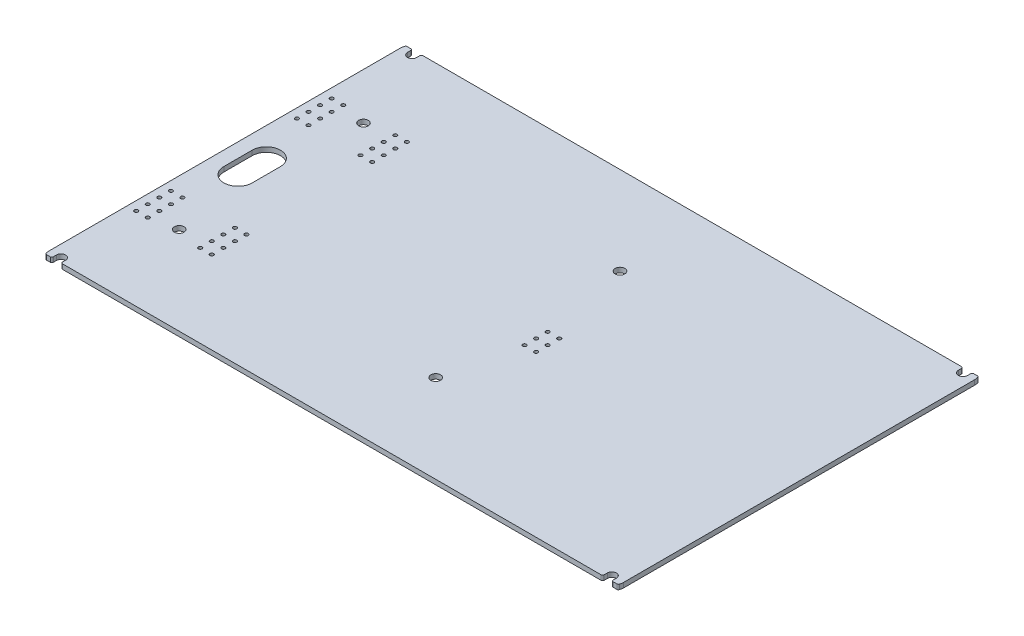
SolidWorks part; units mm, degrees
material "A-Glass Fiber"
ref_plane "Front Plane" through (0, 0, 0) normal (0, 0, 1) x (1, 0, 0)
ref_plane "Top Plane" through (0, 0, 0) normal (0, 1, 0) x (1, 0, 0)
ref_plane "Right Plane" through (0, 0, 0) normal (1, 0, 0) x (0, 0, -1)
sketch "Sketch1" plane through (0, 0, 0) normal (0, 1, 0) x (1, 0, 0)
  line L0 (0, 0) -> (133.1949, 0) construction
  line L2 (-55.9843, -57.8231) -> (-55.9843, 57.8231)
  line L4 (133.1949, -57.8231) -> (133.1949, 57.8231)
  line L8 (-55.6615, 59.3713) -> (132.872, 59.3713)
  line L9 (-55.6615, -59.3713) -> (132.872, -59.3713)
  arc A0 (-55.9843, 57.8231) -> (-55.6615, 59.3713) centre (-52.1108, 57.8231) cw
  arc A1 (132.872, 59.3713) -> (133.1949, 57.8231) centre (129.3214, 57.8231) cw
  arc A2 (133.1949, -57.8231) -> (132.872, -59.3713) centre (129.3214, -57.8231) cw
  arc A3 (-55.6615, -59.3713) -> (-55.9843, -57.8231) centre (-52.1108, -57.8231) cw
  arc A8 (31.0353, 66.8607) -> (46.1753, 66.8607) centre (38.6053, 66.9417) ccw construction
  circle A9 centre (-52.1108, -57.8231) radius 3.8735 construction
  circle A10 centre (129.3214, 57.8231) radius 3.8735 construction
  circle A11 centre (-52.1108, 57.8231) radius 3.8735 construction
  circle A12 centre (129.3214, -57.8231) radius 3.8735 construction
  arc A13 (46.1753, -66.8607) -> (31.0353, -66.8607) centre (38.6053, -66.9417) ccw construction
  point P1 (0, 0)
  point P16 (133.1949, 57.8231)
  point P17 (133.1949, 57.8231)
extrude "Boss-Extrude1" add sketch "Sketch1" against normal blind 1.5875
sketch "Sketch2" plane through (0, 0, 0) normal (0, 1, 0) x (1, 0, 0)
  circle A35 centre (-40.6725, -30.35) radius 1.5875
  circle A36 centre (-40.6725, -30.35) radius 1.5875
  circle A37 centre (-40.6725, 30.35) radius 1.5875
  circle A38 centre (-40.6725, 30.35) radius 1.5875
  circle A39 centre (43.8275, 30.35) radius 1.5875
  circle A40 centre (43.8275, 30.35) radius 1.5875
  circle A41 centre (43.8275, -30.35) radius 1.5875
  circle A42 centre (43.8275, -30.35) radius 1.5875
  dimension "D27" = 0
  dimension "D28" = 0
  dimension "D29" = 0
  dimension "D30" = 0
extrude "Cut-Extrude1" cut sketch "Sketch2" against normal through all
sketch "Sketch3" plane through (0, 0, 0) normal (0, 1, 0) x (1, 0, 0)
  line L5 (-46.6035, 4.285) -> (-46.6035, -5.035) construction
  line L6 (-41.9335, 4.285) -> (-41.9335, -5.035)
  line L7 (-51.2735, 4.285) -> (-51.2735, -5.035)
  line L17 (-43.2035, 3.375) -> (-41.9335, 3.375) construction
  line L18 (-44.8535, 7.2) -> (-44.1998, 8.2889) construction
  line L19 (-46.6035, 7.2) -> (-46.6035, 8.955) construction
  line L20 (-44.8535, 7.2) -> (-48.3535, 7.2) construction
  line L21 (-46.6035, -7.95) -> (-46.6035, -9.705) construction
  line L22 (-48.3535, -7.95) -> (-44.8535, -7.95) construction
  arc A13 (-41.9335, 4.285) -> (-51.2735, 4.285) centre (-46.6035, 4.285) ccw
  arc A14 (-51.2735, -5.035) -> (-41.9335, -5.035) centre (-46.6035, -5.035) ccw
  arc A17 (-44.8535, 0.46) -> (-44.8535, 6.29) centre (-46.6035, 3.375) ccw construction
  point P2 (-46.6035, -0.375)
  dimension "D1" = 1.27
extrude "Cut-Extrude2" cut sketch "Sketch3" against normal through all
sketch "Sketch4" plane through (0, -1.5875, 0) normal (0, -1, 0) x (1, 0, 0)
  line L4 (-34.35, -10.348) -> (-39.27, -10.348)
  line L5 (-34.35, -25.08) -> (-34.35, -10.348)
  line L6 (-39.27, -25.08) -> (-34.35, -25.08)
  line L7 (-39.27, -10.348) -> (-39.27, -25.08)
  line L8 (-34.35, -10.348) -> (-39.27, -10.348)
  line L9 (-34.35, -25.08) -> (-34.35, -10.348)
  line L10 (-39.27, -25.08) -> (-34.35, -25.08)
  line L11 (-39.27, -10.348) -> (-39.27, -25.08)
  line L12 (-34.35, 25.63) -> (-39.27, 25.63)
  line L13 (-34.35, 10.898) -> (-34.35, 25.63)
  line L14 (-39.27, 10.898) -> (-34.35, 10.898)
  line L15 (-39.27, 25.63) -> (-39.27, 10.898)
  line L16 (-34.35, 25.63) -> (-39.27, 25.63)
  line L17 (-34.35, 10.898) -> (-34.35, 25.63)
  line L18 (-39.27, 10.898) -> (-34.35, 10.898)
  line L19 (-39.27, 25.63) -> (-39.27, 10.898)
  line L20 (-44.42, 10.898) -> (-39.5, 10.898)
  line L21 (-39.5, 10.898) -> (-39.5, 25.63)
  line L22 (-39.5, 25.63) -> (-44.42, 25.63)
  line L23 (-44.42, 25.63) -> (-44.42, 10.898)
  line L24 (-44.42, 10.898) -> (-39.5, 10.898)
  line L25 (-39.5, 10.898) -> (-39.5, 25.63)
  line L26 (-39.5, 25.63) -> (-44.42, 25.63)
  line L27 (-44.42, 25.63) -> (-44.42, 10.898)
  line L28 (-39.5, -10.348) -> (-44.42, -10.348)
  line L29 (-39.5, -25.08) -> (-39.5, -10.348)
  line L30 (-44.42, -25.08) -> (-39.5, -25.08)
  line L31 (-44.42, -10.348) -> (-44.42, -25.08)
  line L32 (-39.5, -10.348) -> (-44.42, -10.348)
  line L33 (-39.5, -25.08) -> (-39.5, -10.348)
  line L34 (-44.42, -25.08) -> (-39.5, -25.08)
  line L35 (-44.42, -10.348) -> (-44.42, -25.08)
  line L36 (35.46, 13.148) -> (40.38, 13.148)
  line L37 (35.46, 27.88) -> (35.46, 13.148)
  line L38 (40.38, 27.88) -> (35.46, 27.88)
  line L39 (40.38, 13.148) -> (40.38, 27.88)
  line L40 (35.46, 13.148) -> (40.38, 13.148)
  line L41 (35.46, 27.88) -> (35.46, 13.148)
  line L42 (40.38, 27.88) -> (35.46, 27.88)
  line L43 (40.38, 13.148) -> (40.38, 27.88)
  dimension "D1" = 0
  dimension "D2" = 0
  dimension "D3" = 0
  dimension "D4" = 0
  dimension "D5" = 0
sketch "Sketch6" plane through (0, -1.5875, 0) normal (0, -1, 0) x (1, 0, 0)
  line L0 (-20.19, 27.65) -> (-20.19, 33.65) construction
  line L1 (-20.19, 33.65) -> (-14.19, 33.65) construction
  line L2 (-14.19, 33.65) -> (-14.19, 27.65) construction
  line L3 (-14.19, 27.65) -> (-20.19, 27.65) construction
  line L4 (33.69, -6.45) -> (33.69, -22.45)
  line L5 (54.59, -6.45) -> (33.69, -6.45)
  line L6 (54.59, -22.45) -> (54.59, -6.45)
  line L7 (33.69, -22.45) -> (54.59, -22.45)
  line L8 (33.69, -6.45) -> (33.69, -22.45)
  line L9 (54.59, -6.45) -> (33.69, -6.45)
  line L10 (54.59, -22.45) -> (54.59, -6.45)
  line L11 (33.69, -22.45) -> (54.59, -22.45)
  line L20 (-8.69, 27.65) -> (-8.69, 33.65) construction
  line L21 (-8.69, 33.65) -> (-2.69, 33.65) construction
  line L22 (-2.69, 33.65) -> (-2.69, 27.65) construction
  line L23 (-2.69, 27.65) -> (-8.69, 27.65) construction
  line L24 (-20.19, 27.65) -> (-20.19, 33.65)
  line L25 (-20.19, 33.65) -> (-14.19, 33.65)
  line L26 (-14.19, 33.65) -> (-14.19, 27.65)
  line L27 (-14.19, 27.65) -> (-20.19, 27.65)
  line L28 (-8.69, 27.65) -> (-8.69, 33.65)
  line L29 (-8.69, 33.65) -> (-2.69, 33.65)
  line L30 (-2.69, 33.65) -> (-2.69, 27.65)
  line L31 (-2.69, 27.65) -> (-8.69, 27.65)
  line L80 (55.31, -35.15) -> (55.31, 35.15)
  line L82 (55.31, 35.15) -> (-55.31, 35.15)
  line L84 (-55.31, 35.15) -> (-55.31, -35.15)
  line L86 (-55.31, -35.15) -> (55.31, -35.15)
  line L92 (55.31, -35.15) -> (55.31, 35.15)
  line L94 (55.31, 35.15) -> (-55.31, 35.15)
  line L96 (-55.31, 35.15) -> (-55.31, -35.15)
  line L98 (-55.31, -35.15) -> (55.31, -35.15)
  circle A0 centre (-17.19, 30.65) radius 1.75 construction
  circle A1 centre (-5.69, 30.65) radius 1.75 construction
  circle A2 centre (-17.19, 30.65) radius 1.75
  circle A3 centre (-5.69, 30.65) radius 1.75
  dimension "D1" = 0
  dimension "D2" = 0
sketch "Sketch7" plane through (0, -1.5875, 0) normal (0, -1, 0) x (1, 0, 0)
  circle A1 centre (49.2175, 6.483) radius 0.6
  circle A2 centre (49.2175, 6.483) radius 0.6
  circle A3 centre (-49.1085, -32.125) radius 0.6
  circle A4 centre (-49.1085, -32.125) radius 0.6
  circle A5 centre (-28.1535, -32.125) radius 0.6
  circle A6 centre (-28.1535, -32.125) radius 0.6
  circle A7 centre (-28.1535, 20.707) radius 0.6
  circle A8 centre (-28.1535, 20.707) radius 0.6
  circle A9 centre (-49.2355, 20.707) radius 0.6
  circle A10 centre (-49.2355, 20.707) radius 0.6
  circle A11 centre (-31.9635, 20.707) radius 0.6
  circle A12 centre (-31.9635, 20.707) radius 0.6
  circle A13 centre (-53.0455, 20.707) radius 0.6
  circle A14 centre (-53.0455, 20.707) radius 0.6
  circle A15 centre (-31.9635, 28.327) radius 0.6
  circle A16 centre (-31.9635, 28.327) radius 0.6
  circle A17 centre (-53.0455, 28.327) radius 0.6
  circle A18 centre (-53.0455, 28.327) radius 0.6
  circle A19 centre (-31.9635, 24.517) radius 0.6
  circle A20 centre (-31.9635, 24.517) radius 0.6
  circle A21 centre (-53.0455, 24.517) radius 0.6
  circle A22 centre (-53.0455, 24.517) radius 0.6
  circle A23 centre (-31.9635, -28.315) radius 0.6
  circle A24 centre (-31.9635, -28.315) radius 0.6
  circle A25 centre (-52.9185, -28.315) radius 0.6
  circle A26 centre (-52.9185, -28.315) radius 0.6
  circle A27 centre (-31.9635, -32.125) radius 0.6
  circle A28 centre (-31.9635, -32.125) radius 0.6
  circle A29 centre (-52.9185, -32.125) radius 0.6
  circle A30 centre (-52.9185, -32.125) radius 0.6
  circle A31 centre (-28.1535, 24.517) radius 0.6
  circle A32 centre (-28.1535, 24.517) radius 0.6
  circle A33 centre (-49.2355, 24.517) radius 0.6
  circle A34 centre (-49.2355, 24.517) radius 0.6
  circle A35 centre (-31.9635, 32.137) radius 0.6
  circle A36 centre (-31.9635, 32.137) radius 0.6
  circle A37 centre (-53.0455, 32.137) radius 0.6
  circle A38 centre (-53.0455, 32.137) radius 0.6
  circle A39 centre (-31.9635, -20.695) radius 0.6
  circle A40 centre (-31.9635, -20.695) radius 0.6
  circle A41 centre (-52.9185, -20.695) radius 0.6
  circle A42 centre (-52.9185, -20.695) radius 0.6
  circle A43 centre (-31.9635, -24.505) radius 0.6
  circle A44 centre (-31.9635, -24.505) radius 0.6
  circle A45 centre (-52.9185, -24.505) radius 0.6
  circle A46 centre (-52.9185, -24.505) radius 0.6
  circle A47 centre (-28.1535, 32.137) radius 0.6
  circle A48 centre (-28.1535, 32.137) radius 0.6
  circle A49 centre (-49.2355, 32.137) radius 0.6
  circle A50 centre (-49.2355, 32.137) radius 0.6
  circle A51 centre (-28.1535, 28.327) radius 0.6
  circle A52 centre (-28.1535, 28.327) radius 0.6
  circle A53 centre (-49.2355, 28.327) radius 0.6
  circle A54 centre (-49.2355, 28.327) radius 0.6
  circle A55 centre (-28.1535, -24.505) radius 0.6
  circle A56 centre (-28.1535, -24.505) radius 0.6
  circle A57 centre (-49.1085, -24.505) radius 0.6
  circle A58 centre (-49.1085, -24.505) radius 0.6
  circle A59 centre (-28.1535, -28.315) radius 0.6
  circle A60 centre (-28.1535, -28.315) radius 0.6
  circle A61 centre (-49.1085, -28.315) radius 0.6
  circle A62 centre (-49.1085, -28.315) radius 0.6
  circle A63 centre (49.2175, 2.673) radius 0.6
  circle A64 centre (49.2175, 2.673) radius 0.6
  circle A65 centre (53.0275, -1.137) radius 0.6
  circle A66 centre (53.0275, -1.137) radius 0.6
  circle A67 centre (53.0275, 2.673) radius 0.6
  circle A68 centre (53.0275, 2.673) radius 0.6
  circle A69 centre (53.0275, 6.483) radius 0.6
  circle A70 centre (53.0275, 6.483) radius 0.6
  circle A71 centre (-28.1535, -20.695) radius 0.6
  circle A72 centre (-28.1535, -20.695) radius 0.6
  circle A73 centre (-49.1085, -20.695) radius 0.6
  circle A74 centre (-49.1085, -20.695) radius 0.6
  circle A75 centre (49.2175, -1.137) radius 0.6
  circle A76 centre (49.2175, -1.137) radius 0.6
  dimension "D1" = 0
  dimension "D2" = 0
  dimension "D3" = 0
  dimension "D4" = 0
  dimension "D5" = 0
  dimension "D6" = 0
  dimension "D7" = 0
  dimension "D8" = 0
  dimension "D9" = 0
  dimension "D10" = 0
  dimension "D11" = 0
  dimension "D12" = 0
  dimension "D13" = 0
  dimension "D14" = 0
  dimension "D15" = 0
  dimension "D16" = 0
  dimension "D17" = 0
  dimension "D18" = 0
  dimension "D19" = 0
  dimension "D20" = 0
  dimension "D21" = 0
  dimension "D22" = 0
  dimension "D23" = 0
  dimension "D24" = 0
  dimension "D25" = 0
  dimension "D26" = 0
  dimension "D27" = 0
  dimension "D28" = 0
  dimension "D29" = 0
  dimension "D30" = 0
  dimension "D31" = 0
  dimension "D32" = 0
  dimension "D33" = 0
  dimension "D34" = 0
  dimension "D35" = 0
  dimension "D36" = 0
  dimension "D37" = 0
  dimension "D38" = 0
extrude "Cut-Extrude3" cut sketch "Sketch7" against normal through all
sketch "Sketch8" plane through (0, -1.5875, 0) normal (0, -1, 0) x (1, 0, 0)
  line L4 (-47.9085, -18.395) -> (-54.7585, -18.395)
  line L5 (-47.9085, -34.425) -> (-47.9085, -18.395)
  line L6 (-54.7585, -34.425) -> (-47.9085, -34.425)
  line L7 (-54.7585, -18.395) -> (-54.7585, -34.425)
  line L8 (-47.9085, -18.395) -> (-54.7585, -18.395)
  line L9 (-47.9085, -34.425) -> (-47.9085, -18.395)
  line L10 (-54.7585, -34.425) -> (-47.9085, -34.425)
  line L11 (-54.7585, -18.395) -> (-54.7585, -34.425)
  line L12 (-54.8855, 18.407) -> (-48.0355, 18.407)
  line L13 (-48.0355, 18.407) -> (-48.0355, 34.437)
  line L14 (-48.0355, 34.437) -> (-54.8855, 34.437)
  line L15 (-54.8855, 34.437) -> (-54.8855, 18.407)
  line L16 (-54.8855, 18.407) -> (-48.0355, 18.407)
  line L17 (-48.0355, 18.407) -> (-48.0355, 34.437)
  line L18 (-48.0355, 34.437) -> (-54.8855, 34.437)
  line L19 (-54.8855, 34.437) -> (-54.8855, 18.407)
  line L20 (-33.8035, -18.395) -> (-33.8035, -34.425)
  line L21 (-33.8035, -34.425) -> (-26.9535, -34.425)
  line L22 (-26.9535, -34.425) -> (-26.9535, -18.395)
  line L23 (-26.9535, -18.395) -> (-33.8035, -18.395)
  line L24 (-33.8035, -18.395) -> (-33.8035, -34.425)
  line L25 (-33.8035, -34.425) -> (-26.9535, -34.425)
  line L26 (-26.9535, -34.425) -> (-26.9535, -18.395)
  line L27 (-26.9535, -18.395) -> (-33.8035, -18.395)
  line L28 (-26.9535, 34.437) -> (-33.8035, 34.437)
  line L29 (-26.9535, 18.407) -> (-26.9535, 34.437)
  line L30 (-33.8035, 18.407) -> (-26.9535, 18.407)
  line L31 (-33.8035, 34.437) -> (-33.8035, 18.407)
  line L32 (-26.9535, 34.437) -> (-33.8035, 34.437)
  line L33 (-26.9535, 18.407) -> (-26.9535, 34.437)
  line L34 (-33.8035, 18.407) -> (-26.9535, 18.407)
  line L35 (-33.8035, 34.437) -> (-33.8035, 18.407)
  line L36 (47.8175, 8.783) -> (47.8175, -3.437)
  line L37 (47.8175, -3.437) -> (54.6675, -3.437)
  line L38 (54.6675, -3.437) -> (54.6675, 8.783)
  line L39 (54.6675, 8.783) -> (47.8175, 8.783)
  line L40 (47.8175, 8.783) -> (47.8175, -3.437)
  line L41 (47.8175, -3.437) -> (54.6675, -3.437)
  line L42 (54.6675, -3.437) -> (54.6675, 8.783)
  line L43 (54.6675, 8.783) -> (47.8175, 8.783)
  dimension "D1" = 0
  dimension "D2" = 0
  dimension "D3" = 0
  dimension "D4" = 0
  dimension "D5" = 0
sketch "Sketch9" plane through (0, 0, 0) normal (0, 1, 0) x (1, 0, 0)
  line L0 (130.8214, -57.8231) -> (130.8214, -59.3713)
  line L2 (130.8214, -59.3713) -> (127.8214, -59.3713)
  line L3 (127.8214, -59.3713) -> (127.8214, -57.8231)
  line L4 (-55.6615, -59.3713) -> (132.872, -59.3713) construction
  line L5 (127.8214, 57.8231) -> (127.8214, 59.3713)
  line L6 (132.872, 59.3713) -> (-55.6615, 59.3713) construction
  line L7 (127.8214, 59.3713) -> (130.8214, 59.3713)
  line L8 (130.8214, 59.3713) -> (130.8214, 57.8231)
  line L9 (-50.6108, 57.8231) -> (-50.6108, 59.3713)
  line L10 (-50.6108, 59.3713) -> (-53.6108, 59.3713)
  line L11 (-53.6108, 59.3713) -> (-53.6108, 57.8231)
  line L12 (-53.6108, -57.8231) -> (-53.6108, -59.3713)
  line L13 (-53.6108, -59.3713) -> (-50.6108, -59.3713)
  line L14 (-50.6108, -59.3713) -> (-50.6108, -57.8231)
  arc A0 (-53.6108, 57.8231) -> (-50.6108, 57.8231) centre (-52.1108, 57.8231) ccw
  arc A1 (-50.6108, -57.8231) -> (-53.6108, -57.8231) centre (-52.1108, -57.8231) ccw
  arc A2 (127.8214, 57.8231) -> (130.8214, 57.8231) centre (129.3214, 57.8231) ccw
  arc A3 (130.8214, -57.8231) -> (127.8214, -57.8231) centre (129.3214, -57.8231) ccw
  point P1 (-53.6108, -59.3713)
  dimension "D1" = 3
extrude "Cut-Extrude4" cut sketch "Sketch9" against normal through all
sketch "Sketch11" plane through (0, -1.5875, 0) normal (0, -1, 0) x (1, 0, 0)
  line L0 (140.0352, 31.6837) -> (152.7352, 31.6837) construction
  line L1 (140.0352, 31.6837) -> (152.7352, 31.6837)
sketch "Sketch12" plane through (0, -1.5875, 0) normal (0, -1, 0) x (1, 0, 0)
  circle A0 centre (-40.6725, -30.35) radius 3.81
  circle A1 centre (-40.6725, -30.35) radius 1.5875 construction
  circle A2 centre (-40.6725, 30.35) radius 3.81
  circle A3 centre (43.8275, 30.35) radius 3.81
  circle A4 centre (43.8275, -30.35) radius 3.81
  dimension "D1" = 7.62
sketch "Sketch14" plane through (0, -1.5875, 0) normal (0, -1, 0) x (1, 0, 0)
  line L3 (125.6585, 59.0931) -> (123.9874, 59.0931)
  line L4 (123.9874, 59.0931) -> (123.9874, 56.5531)
  line L5 (123.9874, 56.5531) -> (125.6585, 56.5531)
  line L6 (125.6585, 59.0931) -> (123.9874, 59.0931)
  line L7 (123.9874, 59.0931) -> (123.9874, 56.5531)
  line L8 (123.9874, 56.5531) -> (125.6585, 56.5531)
  line L9 (132.9843, 56.5531) -> (134.6554, 56.5531)
  line L10 (134.6554, 56.5531) -> (134.6554, 59.0931)
  line L11 (134.6554, 59.0931) -> (132.9843, 59.0931)
  line L12 (132.9843, 56.5531) -> (134.6554, 56.5531)
  line L13 (134.6554, 56.5531) -> (134.6554, 59.0931)
  line L14 (134.6554, 59.0931) -> (132.9843, 59.0931)
  line L15 (128.0514, 54.1602) -> (128.0514, 52.4891)
  line L16 (128.0514, 52.4891) -> (130.5914, 52.4891)
  line L17 (130.5914, 52.4891) -> (130.5914, 54.1602)
  line L18 (128.0514, 54.1602) -> (128.0514, 52.4891)
  line L19 (128.0514, 52.4891) -> (130.5914, 52.4891)
  line L20 (130.5914, 52.4891) -> (130.5914, 54.1602)
  line L21 (125.6585, -56.5531) -> (123.9874, -56.5531)
  line L22 (123.9874, -56.5531) -> (123.9874, -59.0931)
  line L23 (123.9874, -59.0931) -> (125.6585, -59.0931)
  line L24 (125.6585, -56.5531) -> (123.9874, -56.5531)
  line L25 (123.9874, -56.5531) -> (123.9874, -59.0931)
  line L26 (123.9874, -59.0931) -> (125.6585, -59.0931)
  line L27 (130.5914, 63.1571) -> (128.0514, 63.1571)
  line L28 (128.0514, 63.1571) -> (128.0514, 61.486)
  line L29 (130.5914, 61.486) -> (130.5914, 63.1571)
  line L30 (130.5914, 63.1571) -> (128.0514, 63.1571)
  line L31 (128.0514, 63.1571) -> (128.0514, 61.486)
  line L32 (130.5914, 61.486) -> (130.5914, 63.1571)
  line L33 (130.5914, -54.1602) -> (130.5914, -52.4891)
  line L34 (130.5914, -52.4891) -> (128.0514, -52.4891)
  line L35 (128.0514, -52.4891) -> (128.0514, -54.1602)
  line L36 (130.5914, -54.1602) -> (130.5914, -52.4891)
  line L37 (130.5914, -52.4891) -> (128.0514, -52.4891)
  line L38 (128.0514, -52.4891) -> (128.0514, -54.1602)
  line L39 (128.0514, -61.486) -> (128.0514, -63.1571)
  line L40 (128.0514, -63.1571) -> (130.5914, -63.1571)
  line L41 (130.5914, -63.1571) -> (130.5914, -61.486)
  line L42 (128.0514, -61.486) -> (128.0514, -63.1571)
  line L43 (128.0514, -63.1571) -> (130.5914, -63.1571)
  line L44 (130.5914, -63.1571) -> (130.5914, -61.486)
  line L45 (134.6554, -59.0931) -> (134.6554, -56.5531)
  line L46 (132.9843, -59.0931) -> (134.6554, -59.0931)
  line L47 (134.6554, -56.5531) -> (132.9843, -56.5531)
  line L48 (134.6554, -59.0931) -> (134.6554, -56.5531)
  line L49 (132.9843, -59.0931) -> (134.6554, -59.0931)
  line L50 (134.6554, -56.5531) -> (132.9843, -56.5531)
  line L51 (-55.7737, -56.5531) -> (-57.4448, -56.5531)
  line L52 (-57.4448, -56.5531) -> (-57.4448, -59.0931)
  line L53 (-57.4448, -59.0931) -> (-55.7737, -59.0931)
  line L54 (-55.7737, -56.5531) -> (-57.4448, -56.5531)
  line L55 (-57.4448, -56.5531) -> (-57.4448, -59.0931)
  line L56 (-57.4448, -59.0931) -> (-55.7737, -59.0931)
  line L57 (-48.4479, -59.0931) -> (-46.7768, -59.0931)
  line L58 (-46.7768, -59.0931) -> (-46.7768, -56.5531)
  line L59 (-46.7768, -56.5531) -> (-48.4479, -56.5531)
  line L60 (-48.4479, -59.0931) -> (-46.7768, -59.0931)
  line L61 (-46.7768, -59.0931) -> (-46.7768, -56.5531)
  line L62 (-46.7768, -56.5531) -> (-48.4479, -56.5531)
  line L63 (-53.3808, -63.1571) -> (-50.8408, -63.1571)
  line L64 (-50.8408, -63.1571) -> (-50.8408, -61.486)
  line L65 (-53.3808, -61.486) -> (-53.3808, -63.1571)
  line L66 (-53.3808, -63.1571) -> (-50.8408, -63.1571)
  line L67 (-50.8408, -63.1571) -> (-50.8408, -61.486)
  line L68 (-53.3808, -61.486) -> (-53.3808, -63.1571)
  line L69 (-50.8408, -54.1602) -> (-50.8408, -52.4891)
  line L70 (-50.8408, -52.4891) -> (-53.3808, -52.4891)
  line L71 (-53.3808, -52.4891) -> (-53.3808, -54.1602)
  line L72 (-50.8408, -54.1602) -> (-50.8408, -52.4891)
  line L73 (-50.8408, -52.4891) -> (-53.3808, -52.4891)
  line L74 (-53.3808, -52.4891) -> (-53.3808, -54.1602)
  line L75 (-50.8408, 61.486) -> (-50.8408, 63.1571)
  line L76 (-50.8408, 63.1571) -> (-53.3808, 63.1571)
  line L77 (-53.3808, 63.1571) -> (-53.3808, 61.486)
  line L78 (-50.8408, 61.486) -> (-50.8408, 63.1571)
  line L79 (-50.8408, 63.1571) -> (-53.3808, 63.1571)
  line L80 (-53.3808, 63.1571) -> (-53.3808, 61.486)
  line L81 (-46.7768, 56.5531) -> (-46.7768, 59.0931)
  line L82 (-48.4479, 56.5531) -> (-46.7768, 56.5531)
  line L83 (-46.7768, 59.0931) -> (-48.4479, 59.0931)
  line L84 (-46.7768, 56.5531) -> (-46.7768, 59.0931)
  line L85 (-48.4479, 56.5531) -> (-46.7768, 56.5531)
  line L86 (-46.7768, 59.0931) -> (-48.4479, 59.0931)
  line L87 (-53.3808, 54.1602) -> (-53.3808, 52.4891)
  line L88 (-53.3808, 52.4891) -> (-50.8408, 52.4891)
  line L89 (-50.8408, 52.4891) -> (-50.8408, 54.1602)
  line L90 (-53.3808, 54.1602) -> (-53.3808, 52.4891)
  line L91 (-53.3808, 52.4891) -> (-50.8408, 52.4891)
  line L92 (-50.8408, 52.4891) -> (-50.8408, 54.1602)
  line L93 (-57.4448, 59.0931) -> (-57.4448, 56.5531)
  line L94 (-57.4448, 56.5531) -> (-55.7737, 56.5531)
  line L95 (-55.7737, 59.0931) -> (-57.4448, 59.0931)
  line L96 (-57.4448, 59.0931) -> (-57.4448, 56.5531)
  line L97 (-57.4448, 56.5531) -> (-55.7737, 56.5531)
  line L98 (-55.7737, 59.0931) -> (-57.4448, 59.0931)
  circle A1 centre (-44.2368, 19.5199) radius 3.8735
  circle A2 centre (-44.2368, 19.5199) radius 3.8735
  circle A3 centre (-44.2368, -19.5199) radius 3.8735
  circle A4 centre (-44.2368, -19.5199) radius 3.8735
  circle A5 centre (121.4474, -19.5199) radius 3.8735
  circle A6 centre (121.4474, -19.5199) radius 3.8735
  circle A7 centre (121.4474, 19.5199) radius 3.8735
  circle A8 centre (121.4474, 19.5199) radius 3.8735
  circle A9 centre (129.3214, -57.8231) radius 3.8735
  circle A10 centre (129.3214, -57.8231) radius 3.8735
  circle A11 centre (129.3214, 57.8231) radius 3.8735
  circle A12 centre (129.3214, 57.8231) radius 3.8735
  arc A13 (125.6585, 59.0931) -> (125.6585, 56.5531) centre (129.3214, 57.8231) ccw
  arc A14 (125.6585, 59.0931) -> (125.6585, 56.5531) centre (129.3214, 57.8231) ccw
  arc A15 (132.9843, 56.5531) -> (132.9843, 59.0931) centre (129.3214, 57.8231) ccw
  arc A16 (132.9843, 56.5531) -> (132.9843, 59.0931) centre (129.3214, 57.8231) ccw
  circle A17 centre (-52.1108, 57.8231) radius 3.8735
  circle A18 centre (-52.1108, 57.8231) radius 3.8735
  circle A19 centre (-52.1108, -57.8231) radius 3.8735
  circle A20 centre (-52.1108, -57.8231) radius 3.8735
  arc A21 (128.0514, 54.1602) -> (130.5914, 54.1602) centre (129.3214, 57.8231) ccw
  arc A22 (128.0514, 54.1602) -> (130.5914, 54.1602) centre (129.3214, 57.8231) ccw
  arc A23 (125.6585, -56.5531) -> (125.6585, -59.0931) centre (129.3214, -57.8231) ccw
  arc A24 (125.6585, -56.5531) -> (125.6585, -59.0931) centre (129.3214, -57.8231) ccw
  arc A25 (130.5914, 61.486) -> (128.0514, 61.486) centre (129.3214, 57.8231) ccw
  arc A26 (130.5914, 61.486) -> (128.0514, 61.486) centre (129.3214, 57.8231) ccw
  arc A27 (130.5914, -54.1602) -> (128.0514, -54.1602) centre (129.3214, -57.8231) ccw
  arc A28 (130.5914, -54.1602) -> (128.0514, -54.1602) centre (129.3214, -57.8231) ccw
  arc A29 (128.0514, -61.486) -> (130.5914, -61.486) centre (129.3214, -57.8231) ccw
  arc A30 (128.0514, -61.486) -> (130.5914, -61.486) centre (129.3214, -57.8231) ccw
  arc A31 (132.9843, -59.0931) -> (132.9843, -56.5531) centre (129.3214, -57.8231) ccw
  arc A32 (132.9843, -59.0931) -> (132.9843, -56.5531) centre (129.3214, -57.8231) ccw
  arc A33 (-55.7737, -56.5531) -> (-55.7737, -59.0931) centre (-52.1108, -57.8231) ccw
  arc A34 (-55.7737, -56.5531) -> (-55.7737, -59.0931) centre (-52.1108, -57.8231) ccw
  arc A35 (-48.4479, -59.0931) -> (-48.4479, -56.5531) centre (-52.1108, -57.8231) ccw
  arc A36 (-48.4479, -59.0931) -> (-48.4479, -56.5531) centre (-52.1108, -57.8231) ccw
  arc A37 (-53.3808, -61.486) -> (-50.8408, -61.486) centre (-52.1108, -57.8231) ccw
  arc A38 (-53.3808, -61.486) -> (-50.8408, -61.486) centre (-52.1108, -57.8231) ccw
  arc A39 (-50.8408, -54.1602) -> (-53.3808, -54.1602) centre (-52.1108, -57.8231) ccw
  arc A40 (-50.8408, -54.1602) -> (-53.3808, -54.1602) centre (-52.1108, -57.8231) ccw
  arc A41 (-50.8408, 61.486) -> (-53.3808, 61.486) centre (-52.1108, 57.8231) ccw
  arc A42 (-50.8408, 61.486) -> (-53.3808, 61.486) centre (-52.1108, 57.8231) ccw
  arc A43 (-48.4479, 56.5531) -> (-48.4479, 59.0931) centre (-52.1108, 57.8231) ccw
  arc A44 (-48.4479, 56.5531) -> (-48.4479, 59.0931) centre (-52.1108, 57.8231) ccw
  arc A45 (-53.3808, 54.1602) -> (-50.8408, 54.1602) centre (-52.1108, 57.8231) ccw
  arc A46 (-53.3808, 54.1602) -> (-50.8408, 54.1602) centre (-52.1108, 57.8231) ccw
  arc A47 (-55.7737, 59.0931) -> (-55.7737, 56.5531) centre (-52.1108, 57.8231) ccw
  arc A48 (-55.7737, 59.0931) -> (-55.7737, 56.5531) centre (-52.1108, 57.8231) ccw
  dimension "D1" = 0
  dimension "D2" = 0
  dimension "D3" = 0
  dimension "D4" = 0
  dimension "D5" = 0
  dimension "D6" = 0
  dimension "D7" = 0
  dimension "D8" = 0
  dimension "D9" = 0
  dimension "D10" = 0
  dimension "D11" = 0
  dimension "D12" = 0
  dimension "D13" = 0
  dimension "D14" = 0
  dimension "D15" = 0
  dimension "D16" = 0
  dimension "D17" = 0
  dimension "D18" = 0
  dimension "D19" = 0
  dimension "D20" = 0
  dimension "D21" = 0
  dimension "D22" = 0
  dimension "D23" = 0
  dimension "D24" = 0
fillet "Fillet1" radius 0.508 12 edges at (-50.6108, -0.7937, 59.3713) (-53.6108, -0.7937, 59.3713) (-55.6615, -0.7937, 59.3713) (127.8214, -0.7937, 59.3713) (130.8214, -0.7937, 59.3713) (132.872, -0.7937, 59.3713) (132.872, -0.7937, -59.3713) (130.8214, -0.7937, -59.3713) (127.8214, -0.7937, -59.3713) (-55.6615, -0.7937, -59.3713) (-53.6108, -0.7937, -59.3713) (-50.6108, -0.7937, -59.3713)
equation "\"62.5mi\"=0.1"
